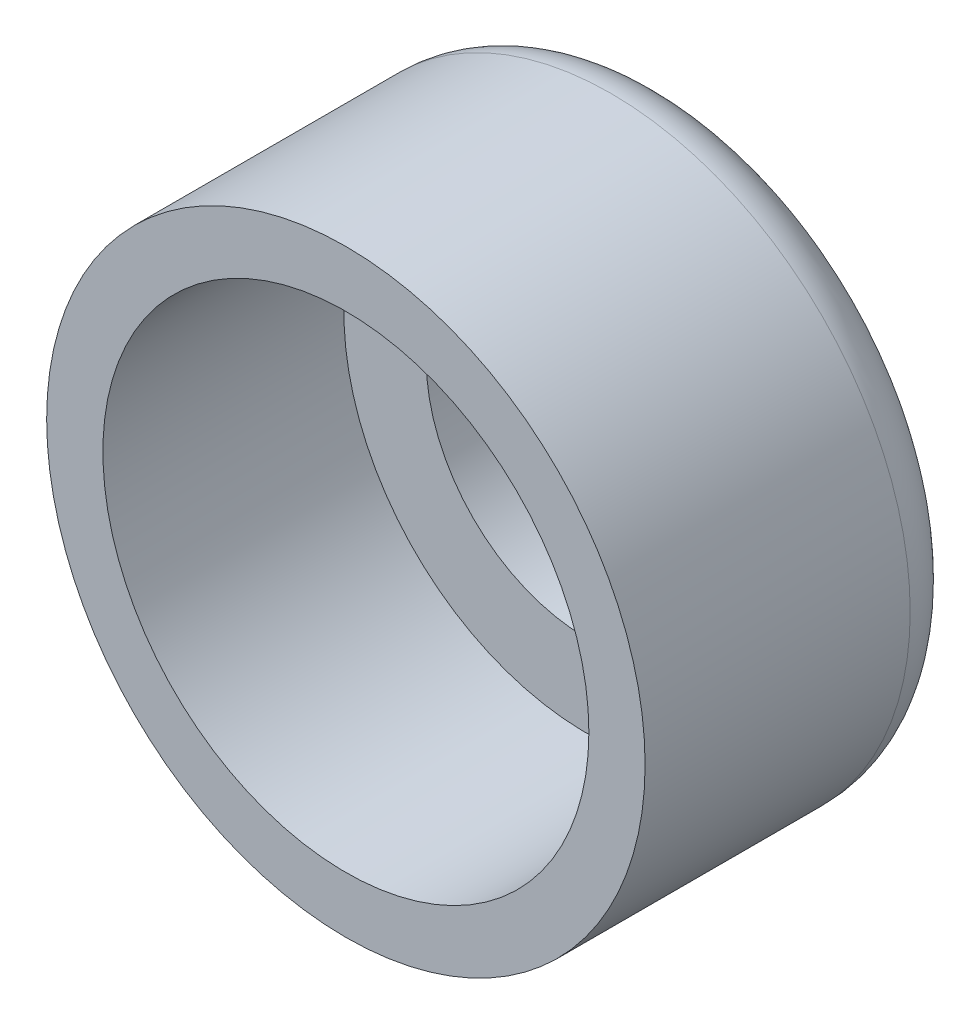
SolidWorks part; units mm, degrees
ref_plane "Front Plane" through (0, 0, 0) normal (1, 0, 0) x (0, 1, 0)
ref_plane "Top Plane" through (0, 0, 0) normal (0, 0, 1) x (0, 1, 0)
ref_plane "Right Plane" through (0, 0, 0) normal (0, 1, 0) x (-1, 0, 0)
ref_axis "x axis" through (-88.99, 0, 0) along (1, 0, 0)
ref_axis "y xxis" through (0, 88.99, 0) along (0, -1, 0)
ref_axis "z axis" through (0, 0, 55) along (0, 0, -1)
sketch "Sketch1" plane through (0, 0, 0) normal (0, 0, 1) x (0, 1, 0)
  circle A0 centre (0, 0) radius 2
  circle A1 centre (0, 0) radius 3.725
  circle A2 centre (0, 0) radius 3.025 construction
  dimension "D1" = 6.05
  dimension "D2" = 0.7
  dimension "D3" = 4
extrude "Boss-Extrude1" add sketch "Sketch1" along normal blind 1
sketch "Sketch2" plane through (0, 0, 1) normal (0, 0, 1) x (1, 0, 0)
  circle A0 centre (0, 0) radius 3.025
  circle A1 centre (0, 0) radius 3.725
  circle A2 centre (0, 0) radius 3.025 construction
  circle A3 centre (0, 0) radius 3.725 construction
extrude "Boss-Extrude2" add sketch "Sketch2" along normal blind 3
fillet "Fillet1" radius 0.7 1 edges at (3.725, 0, 0)
